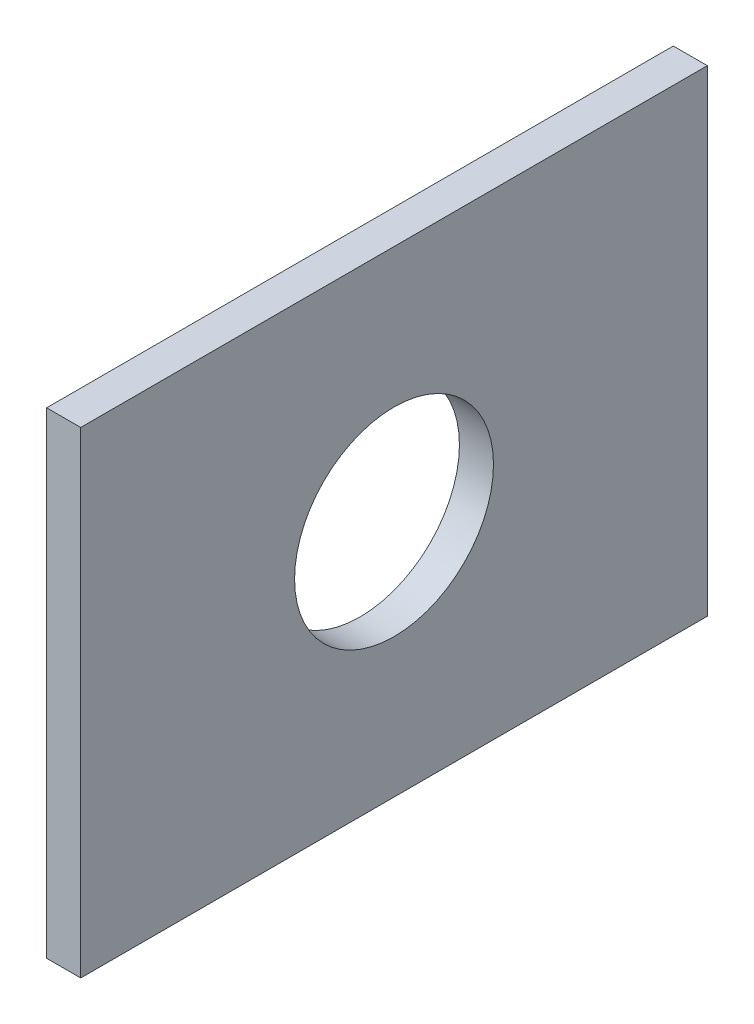
SolidWorks part; units mm, degrees
ref_plane "Front Plane" through (0, 0, 0) normal (0, 0, 1) x (1, 0, 0)
ref_plane "Top Plane" through (0, 0, 0) normal (0, 1, 0) x (1, 0, 0)
ref_plane "Right Plane" through (0, 0, 0) normal (1, 0, 0) x (0, 0, -1)
sketch "Sketch1" plane through (0, 0, 0) normal (1, 0, 0) x (0, 0, -1)
  line L0 (0, 0) -> (92, -70) construction
  line L1 (0, 0) -> (92, 0)
  line L2 (0, 0) -> (0, -70)
  line L3 (0, -70) -> (92, -70)
  line L4 (92, 0) -> (92, -70)
  line L5 (92, 0) -> (0, -70) construction
  line L6 (46, -35) -> (46, 0) construction
  line L7 (46, -17.5) -> (0, -17.5) construction
  circle A0 centre (46, -35) radius 14.6
  dimension "D3" = 29.2
  dimension "D1" = 70
  dimension "D2" = 92
extrude "Boss-Extrude1" add sketch "Sketch1" along normal blind 5
sketch "Sketch2" plane through (5, 0, 0) normal (1, 0, 0) x (0, 0, -1)
  line L0 (0, 0) -> (92, -70) construction
  line L1 (92, -70) -> (92, 0) construction
  line L2 (92, 0) -> (0, -70) construction
